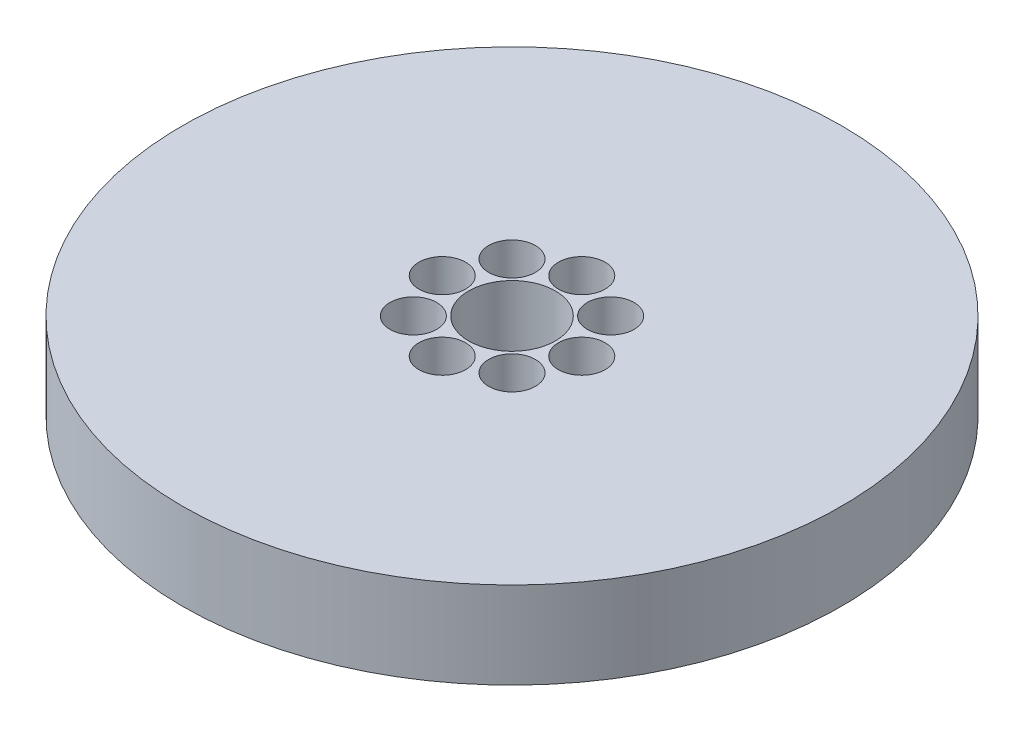
SolidWorks part; units mm, degrees
ref_plane "Front Plane" through (0, 0, 0) normal (0, 0, 1) x (1, 0, 0)
ref_plane "Top Plane" through (0, 0, 0) normal (0, 1, 0) x (1, 0, 0)
ref_plane "Right Plane" through (0, 0, 0) normal (1, 0, 0) x (0, 0, -1)
sketch "Sketch1" plane through (0, 0, 0) normal (0, 1, 0) x (1, 0, 0)
  circle A0 centre (0, 0) radius 95
  dimension "FLANGE_OD" = 190
extrude "Boss-Extrude1" add sketch "Sketch1" along normal blind 25
sketch "Sketch2" plane through (0, 0, 0) normal (0, 1, 0) x (1, 0, 0)
  circle A0 centre (0, 0) radius 12.5
  dimension "BORE_D" = 25
extrude "Cut-Extrude1" cut sketch "Sketch2" along normal through all
sketch "Sketch3" plane through (0, 25, 0) normal (0, 1, 0) x (1, 0, 0)
  circle A0 centre (0, 0) radius 20.1113 construction
  circle A1 centre (-20.1113, 0) radius 6.7372
  dimension "BOLT_D" = 13.4745
  dimension "BOLT_PCD" = 40.2226
extrude "Cut-Extrude2" cut sketch "Sketch3" against normal blind 19.2711
pattern_circular "CirPattern1" count 8 over 360 about axis through (0, 0, 0) along (0, 1, 0) of "Cut-Extrude2"
